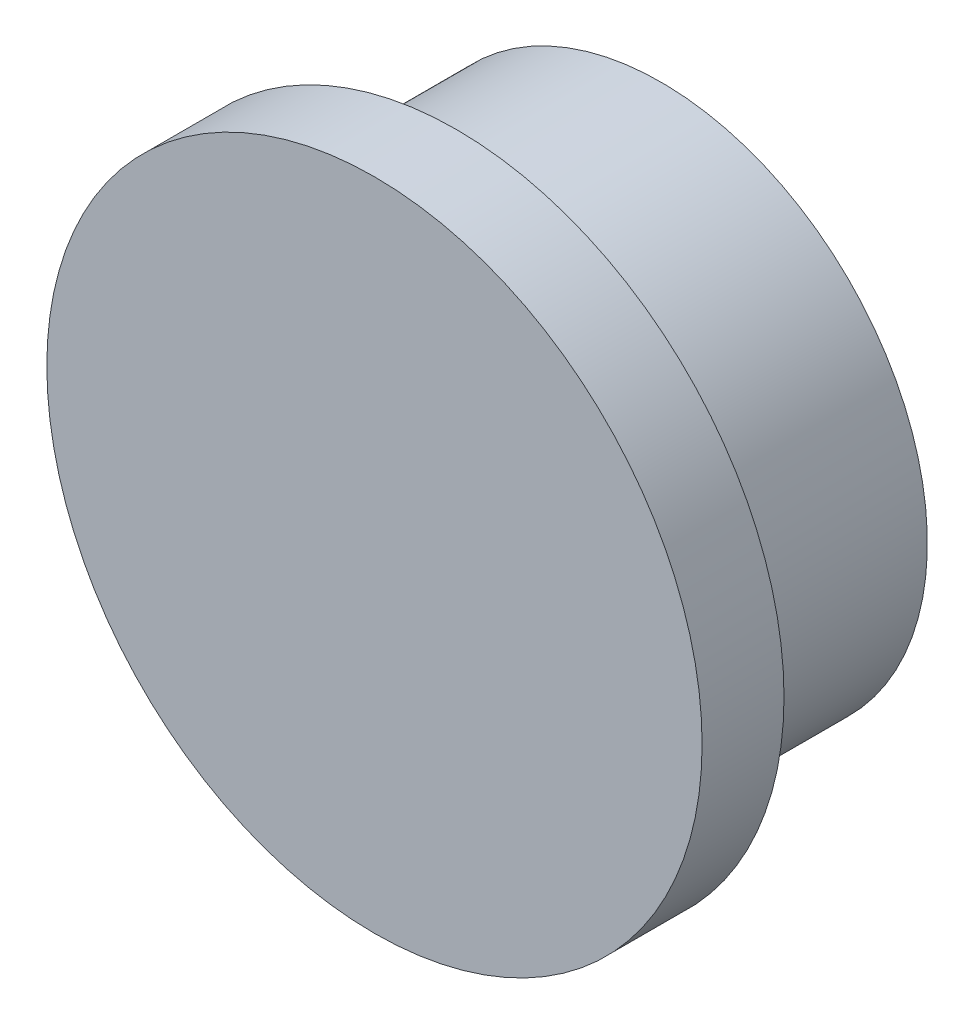
SolidWorks part; units mm, degrees
ref_plane "Front Plane" through (0, 0, 0) normal (0, 0, 1) x (1, 0, 0)
ref_plane "Top Plane" through (0, 0, 0) normal (0, 1, 0) x (1, 0, 0)
ref_plane "Right Plane" through (0, 0, 0) normal (1, 0, 0) x (0, 0, -1)
sketch "Sketch1" plane through (0, 0, 0) normal (0, 0, 1) x (1, 0, 0)
  circle A0 centre (-127.9925, 40.1033) radius 12
extrude "Boss-Extrude1" add sketch "Sketch1" along normal blind 3
sketch "Sketch2" plane through (0, 0, 0) normal (0, 0, -1) x (-1, 0, 0)
  circle A1 centre (127.9925, 40.1033) radius 9.75
extrude "Boss-Extrude2" add sketch "Sketch2" along normal blind 7.5
sketch "Sketch3" plane through (0, 0, -7.5) normal (0, 0, -1) x (-1, 0, 0)
  circle A1 centre (127.9925, 40.1033) radius 1.5
extrude "Cut-Extrude1" cut sketch "Sketch3" against normal blind 5
